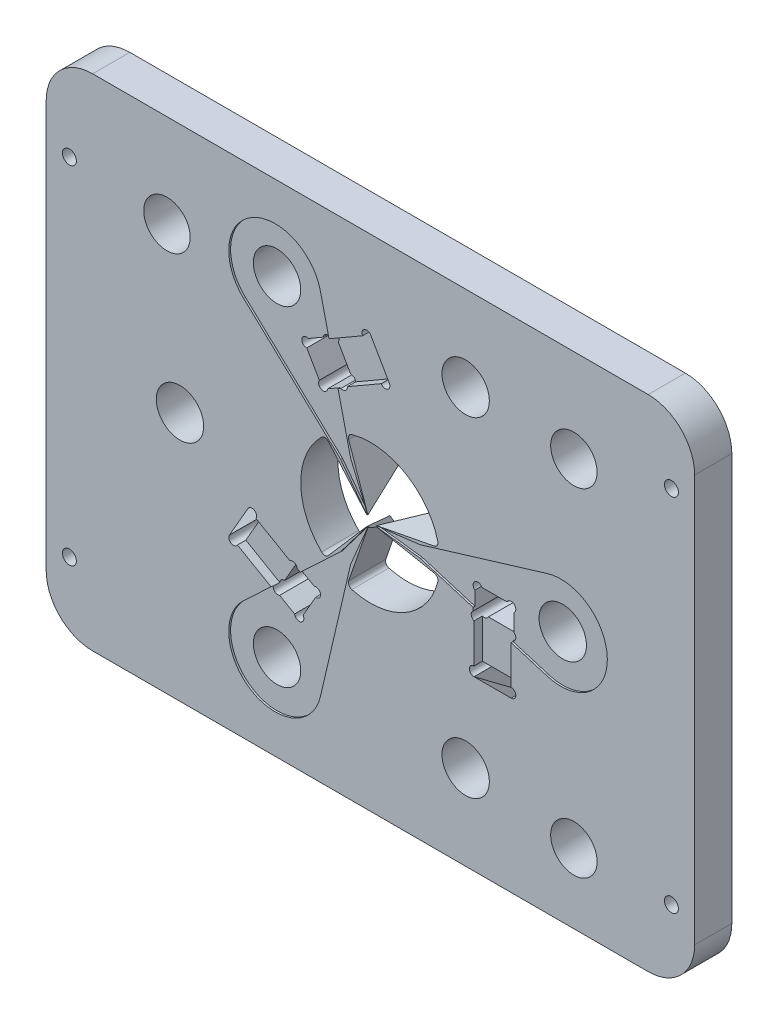
SolidWorks part; units mm, degrees
ref_plane "前基準面" through (0, 0, 0) normal (0, 0, 1) x (1, 0, 0)
ref_plane "上基準面" through (0, 0, 0) normal (0, 1, 0) x (1, 0, 0)
ref_plane "右基準面" through (0, 0, 0) normal (1, 0, 0) x (0, 0, -1)
sketch "草圖1" plane through (0, 0, 0) normal (0, 0, 1) x (1, 0, 0)
  line L1 (-38, 30) -> (38, 30)
  line L2 (-38, 30) -> (-38, -30)
  line L3 (-38, -30) -> (38, -30)
  line L4 (38, 30) -> (38, -30)
  line L5 (-38, 30) -> (38, -30) construction
  line L6 (-38, -30) -> (38, 30) construction
  point P0 (0, 0)
  point P28 (0, 0)
  dimension "D1" = 76
  dimension "D2" = 60
extrude "填料-伸長1" add sketch "草圖1" along normal blind 4
sketch "草圖2" plane through (0, 0, 4) normal (0, 0, 1) x (1, 0, 0)
  line L6 (0.3574, 0.005) -> (20.1903, 2.4807) construction
  line L7 (0.3574, -0.005) -> (20.1903, -2.4807) construction
  line L8 (0.3574, 0.005) -> (4.5094, 0.5233)
  line L9 (0.3574, -0.005) -> (4.5094, -0.5233)
  line L10 (6.1751, 0.8773) -> (19.0478, 4.7845)
  line L11 (6.1751, -0.8773) -> (19.0478, -4.7845)
  line L12 (-2.3278, -5.7864) -> (-5.3804, -18.8881)
  line L13 (-0.1744, -0.312) -> (-1.8015, -4.1669)
  line L14 (-0.183, -0.307) -> (-2.7079, -3.6436)
  line L15 (-3.8473, -4.9091) -> (-13.6674, -14.1037)
  line L16 (-3.8473, 4.9091) -> (-13.6674, 14.1037)
  line L17 (-0.183, 0.307) -> (-2.7079, 3.6436)
  line L18 (-0.1744, 0.312) -> (-1.8015, 4.1669)
  line L19 (-2.3278, 5.7864) -> (-5.3804, 18.8881)
  circle A7 centre (0, 0) radius 0.353 construction
  arc A8 (0.3574, 0.005) -> (0.3574, -0.005) centre (0.358, 0) ccw
  arc A9 (19.0478, -4.7845) -> (19.0478, 4.7845) centre (20.5, 0) ccw
  circle A10 centre (20.5, 0) radius 2.5 construction
  arc A11 (4.5094, -0.5233) -> (6.1751, -0.8773) centre (3.2707, -10.4463) cw
  arc A12 (4.5094, 0.5233) -> (6.1751, 0.8773) centre (3.2707, 10.4463) ccw
  arc A13 (-13.6674, -14.1037) -> (-5.3804, -18.8881) centre (-10.25, -17.7535) ccw
  arc A14 (-1.8015, -4.1669) -> (-2.3278, -5.7864) centre (7.4114, -8.0556) ccw
  arc A15 (-0.1744, -0.312) -> (-0.183, -0.307) centre (-0.179, -0.31) ccw
  arc A16 (-2.7079, -3.6436) -> (-3.8473, -4.9091) centre (-10.6821, 2.3906) cw
  arc A17 (-5.3804, 18.8881) -> (-13.6674, 14.1037) centre (-10.25, 17.7535) ccw
  arc A18 (-2.7079, 3.6436) -> (-3.8473, 4.9091) centre (-10.6821, -2.3906) ccw
  arc A19 (-0.183, 0.307) -> (-0.1744, 0.312) centre (-0.179, 0.31) ccw
  arc A20 (-1.8015, 4.1669) -> (-2.3278, 5.7864) centre (7.4114, 8.0556) cw
  point P17 (5.3574, -0.6291)
  point P20 (5.3574, 0.6291)
  point P46 (0, 0)
  dimension "D1" = 0.706
  dimension "D2" = 0.01
  dimension "D3" = 10
  dimension "D6" = 5
  dimension "D4" = 5
  dimension "D7" = 10
  dimension "D9" = 0.6201
  dimension "D5" = 20.5
  dimension "D8" = 3
extrude "除料-伸長1" cut sketch "草圖2" against normal blind 0.5
sketch "草圖3" plane through (0, 0, 3.5) normal (0, 0, 1) x (1, 0, 0)
  circle A0 centre (20.5, 0) radius 2.55
  circle A3 centre (-10.25, -17.7535) radius 2.55
  circle A4 centre (-10.25, 17.7535) radius 2.55
  point P9 (0, 0)
  dimension "D1" = 5.1
  dimension "D2" = 3
extrude "除料-伸長2" cut sketch "草圖3" against normal through all
sketch "草圖5" plane through (0, 0, 4) normal (0, 0, 1) x (1, 0, 0)
  circle A0 centre (-20.5, 0) radius 2.55
  circle A3 centre (10.25, 17.7535) radius 2.55
  circle A4 centre (10.25, -17.7535) radius 2.55
  point P9 (0, 0)
  dimension "D1" = 5.1
  dimension "D3" = 3
  dimension "D2" = 20.5
extrude "除料-伸長4" cut sketch "草圖5" against normal through all
sketch "草圖6" plane through (0, 0, 4) normal (0, 0, 1) x (1, 0, 0)
  line L0 (-29.9, 26.9) -> (29.9, 26.9)
  line L1 (-38, 30) -> (-38, -30) construction
  line L2 (38, -30) -> (38, 30) construction
  line L3 (-29.9, -26.9) -> (29.9, -26.9)
  line L4 (38, 30) -> (-38, 30) construction
  line L5 (-38, -30) -> (38, -30) construction
  line L6 (-34.9, 21.9) -> (-34.9, -21.9)
  line L7 (34.9, 21.9) -> (34.9, -21.9)
  arc A0 (34.9, 21.9) -> (29.9, 26.9) centre (29.9, 21.9) ccw
  arc A1 (29.9, -26.9) -> (34.9, -21.9) centre (29.9, -21.9) ccw
  arc A2 (-29.9, -26.9) -> (-34.9, -21.9) centre (-29.9, -21.9) cw
  arc A3 (-34.9, 21.9) -> (-29.9, 26.9) centre (-29.9, 21.9) cw
  line M32 (38, -30) -> (38, 30)
  line M33 (38, 30) -> (-38, 30)
  line M34 (-38, 30) -> (-38, -30)
  line M35 (-38, -30) -> (38, -30)
  dimension "D5" = 5
  dimension "D1" = 3.1
  dimension "D2" = 3.1
  dimension "D3" = 3.1
  dimension "D4" = 3.1
extrude "除料-伸長5" cut sketch "草圖6" against normal blind 10 contours L6 A3 L0 A0 L7 A1 L3 A2 M35 M32 M33 M34 region at (0, -29.0317, 4)
ref_plane "平面1" through (0, 0, 4) normal (0, 0, 1) x (1, 0, 0)
sketch "草圖7" plane through (0, 0, 4) normal (0, 0, 1) x (1, 0, 0)
  line L0 (0, 0) -> (34.9, 0) construction
  line L1 (34.9, 21.9) -> (34.9, -21.9) construction
  line L2 (11.05, -0.2286) -> (15.25, -0.2286)
  line L3 (15.25, -0.2286) -> (15.25, -3.3286)
  line L4 (15.25, -3.3286) -> (11.05, -3.3286)
  line L5 (11.05, -3.3286) -> (11.05, -0.2286)
  line L6 (13.15, -0.2286) -> (13.15, -3.3286) construction
  line L7 (11.05, -1.7786) -> (15.25, -1.7786) construction
  line L8 (13.15, -1.7786) -> (11.05, -0.2286) construction
  line L13 (0, 0) -> (-12.75, 22.0836) construction
  line L14 (-6.575, 11.3882) -> (11.1068, 21.5968) construction
  line L15 (-7.4271, 13.3212) -> (-5.3271, 9.6839)
  line L20 (-7.4271, 13.3212) -> (-4.7424, 14.8712)
  line L21 (-4.7424, 14.8712) -> (-2.6424, 11.2339)
  line L22 (-2.6424, 11.2339) -> (-5.3271, 9.6839)
  line L23 (13.15, -1.7786) -> (13.15, -13.7786) construction
  line L24 (11.15, -7.7786) -> (15.15, -7.7786)
  line L25 (15.15, -7.7786) -> (15.15, -8.7786)
  line L26 (15.15, -8.7786) -> (11.15, -8.7786)
  line L27 (11.15, -8.7786) -> (11.15, -7.7786)
  line L28 (11.15, -8.2786) -> (15.15, -8.2786) construction
  line L29 (-6.0847, 14.0962) -> (-3.9847, 10.4589) construction
  line L34 (-7.4271, 13.3212) -> (-2.6424, 11.2339) construction
  line L35 (-4.7424, 14.8712) -> (-5.3271, 9.6839) construction
  line L40 (-0.8386, 17.0096) -> (1.1614, 13.5455)
  line L41 (-0.8386, 17.0096) -> (0.0275, 17.5096)
  line L42 (0.0275, 17.5096) -> (2.0275, 14.0455)
  line L43 (2.0275, 14.0455) -> (1.1614, 13.5455)
  line L44 (-0.4055, 17.2596) -> (1.5945, 13.7955) construction
  line L45 (0, 0) -> (-12.75, -22.0836) construction
  line L46 (-6.575, -11.3882) -> (-21.3666, -2.8483) construction
  line L47 (-5.7229, -9.4553) -> (-7.8229, -13.0926)
  line L48 (-5.7229, -9.4553) -> (-8.4076, -7.9053)
  line L49 (-8.4076, -7.9053) -> (-10.5076, -11.5426)
  line L50 (-10.5076, -11.5426) -> (-7.8229, -13.0926)
  line L51 (-7.0653, -8.6803) -> (-9.1653, -12.3176) construction
  line L52 (-8.4076, -7.9053) -> (-7.8229, -13.0926) construction
  line L53 (-10.5076, -11.5426) -> (-5.7229, -9.4553) construction
  line L54 (-12.3114, -5.7669) -> (-14.3114, -9.231)
  line L55 (-12.3114, -5.7669) -> (-13.1775, -5.2669)
  line L56 (-13.1775, -5.2669) -> (-15.1775, -8.731)
  line L57 (-15.1775, -8.731) -> (-14.3114, -9.231)
  line L58 (-12.7445, -5.5169) -> (-14.7445, -8.981) construction
  line L59 (-4.7841, 14.5007) -> (-3.8841, 12.9418) construction
  line L60 (-10.1659, -11.3935) -> (-9.2659, -9.8347) construction
  circle A0 centre (11.35, -0.45) radius 0.5
  circle A1 centre (14.95, -0.45) radius 0.5
  circle A2 centre (14.95, -3.1071) radius 0.5
  circle A3 centre (11.35, -3.1071) radius 0.5
  circle A4 centre (13.15, -0.9886) radius 0.15 construction
  arc A11 (-5.3804, 18.8881) -> (-13.6674, 14.1037) centre (-10.25, 17.7535) ccw construction
  circle A17 centre (-7.0853, 13.1721) radius 0.5
  circle A18 centre (11.15, -8.2786) radius 0.5
  circle A19 centre (15.15, -8.2786) radius 0.5
  circle A24 centre (-4.7841, 14.5007) radius 0.5
  circle A25 centre (-2.9841, 11.383) radius 0.5
  circle A26 centre (-5.2853, 10.0544) radius 0.5
  circle A27 centre (-0.4055, 17.2596) radius 0.5
  circle A28 centre (1.5945, 13.7955) radius 0.5
  arc A29 (-13.6674, -14.1037) -> (-5.3804, -18.8881) centre (-10.25, -17.7535) ccw construction
  circle A30 centre (-6.0647, -9.6044) radius 0.5
  circle A31 centre (-7.8647, -12.7221) radius 0.5
  circle A32 centre (-10.1659, -11.3935) radius 0.5
  circle A33 centre (-8.3659, -8.2758) radius 0.5
  circle A34 centre (-14.7445, -8.981) radius 0.5
  circle A35 centre (-12.7445, -5.5169) radius 0.5
  point P36 (-6.3771, 11.5025)
  point P43 (0.1614, 15.2775)
  point P66 (-6.7729, -11.2739)
  point P72 (13.15, -7.7786)
  point P81 (-13.3114, -7.4989)
  dimension "D3" = 1
  dimension "D4" = 0.3
  dimension "D10" = 13.15
  dimension "D16" = 1
  dimension "D19" = 4
  dimension "D26" = 1
  dimension "D1" = 4.2
  dimension "D2" = 3.1
  dimension "D5" = 0.79
  dimension "D8" = 0.45
  dimension "D9" = 13.15
  dimension "D11" = 4.2
  dimension "D12" = 3.1
  dimension "D13" = 4
  dimension "D14" = 1
  dimension "D15" = 4.95
  dimension "D17" = 0.3
  dimension "D18" = 0.45
  dimension "D20" = 1
  dimension "D21" = 4.95
  dimension "D22" = 0.3
  dimension "D23" = 13.15
  dimension "D24" = 4.2
  dimension "D25" = 3.1
  dimension "D27" = 0.3
  dimension "D28" = 0.45
  dimension "D29" = 4
  dimension "D30" = 1
  dimension "D31" = 4.95
extrude "除料-伸長6" cut sketch "草圖7" against normal through all contours A17 | A28 L42 A27 L40 | L48 A33 L49 A32 L50 A31 L47 A30 | A35 L56 A34 L54 | A1 | A0 | L5 L2 L3 L4 | A3 | A2 | A17 | A19 | L26 L27 L24 L25 | A18 | A24 | A26 | A25 | A28 | A27 | A31 | A32 | A30 | A33 | A35 | A34 region at (-5.0347, 12.2775, 4) region at (0.5945, 15.5275, 4) region at (-8.1153, -10.4989, 4) region at (-13.7445, -7.2489, 4)
sketch "草圖8" plane through (0, 0, 0) normal (0, 0, 1) x (1, 0, 0)
  line L0 (-34.9, 21.9) -> (-24.9, 21.9) construction
  line L1 (-24.9, 21.9) -> (-24.9, -21.9) construction
  line L2 (-24.9, -21.9) -> (-34.9, -21.9) construction
  line L3 (-34.9, -21.9) -> (-34.9, 21.9) construction
  line L4 (-34.9, 0) -> (34.9, 0) construction
  line L5 (34.9, 21.9) -> (34.9, -21.9) construction
  line L6 (0, 26.9) -> (0, -26.9) construction
  line L7 (-29.9, 26.9) -> (29.9, 26.9) construction
  line L8 (-29.9, -26.9) -> (29.9, -26.9) construction
  circle A0 centre (-32.4, 17.9) radius 0.75
  circle A3 centre (32.4, 19.4) radius 0.75
  circle A4 centre (32.4, -19.4) radius 0.75
  circle A5 centre (-32.4, -19.4) radius 0.75
  dimension "D2" = 1.5
  dimension "D5" = 1.5
  dimension "D7" = 2.5
  dimension "D1" = 10
  dimension "D3" = 4
  dimension "D4" = 2.5
  dimension "D6" = 2.5
extrude "除料-伸長7" cut sketch "草圖8" along normal through all contours A3 | A5 | A4 | A0 region at (32.4, 19.4, 0) region at (-32.4, -19.4, 0)
sketch "草圖10" plane through (0, 0, 3.5) normal (0, 0, 1) x (1, 0, 0)
  line L48 (-3.8473, -4.9091) -> (-7.5662, -8.3911) construction
  line L49 (-7.5662, -8.3911) -> (-6.2611, -9.1446) construction
  line L50 (-6.0971, -10.1033) -> (-7.4488, -12.4446) construction
  line L51 (-8.3611, -12.7819) -> (-9.9695, -11.8533) construction
  line L52 (-10.6531, -11.2814) -> (-13.6674, -14.1037) construction
  line L53 (-5.3804, -18.8881) -> (-2.3278, -5.7864) construction
  line L54 (-1.8015, -4.1669) -> (-0.1744, -0.312) construction
  line L55 (-0.183, -0.307) -> (-2.7079, -3.6436) construction
  line L56 (11.05, -2.357) -> (11.05, -0.85) construction
  line L57 (11.7983, -0.2286) -> (14.5017, -0.2286) construction
  line L58 (15.25, -0.85) -> (15.25, -2.7071) construction
  line L59 (15.0966, -3.5852) -> (19.0478, -4.7845) construction
  line L60 (19.0478, 4.7845) -> (6.1751, 0.8773) construction
  line L61 (4.5094, 0.5233) -> (0.3574, 0.005) construction
  line L62 (0.3574, -0.005) -> (4.5094, -0.5233) construction
  line L63 (6.1751, -0.8773) -> (11.05, -2.357) construction
  line L64 (-3.4838, 10.7481) -> (-4.7889, 9.9946) construction
  line L65 (-5.7012, 10.3319) -> (-7.0529, 12.6731) construction
  line L66 (-6.8889, 13.6319) -> (-5.2805, 14.5605) construction
  line L67 (-4.4434, 14.8666) -> (-5.3804, 18.8881) construction
  line L68 (-13.6674, 14.1037) -> (-3.8473, 4.9091) construction
  line L69 (-2.7079, 3.6436) -> (-0.183, 0.307) construction
  line L70 (-0.1744, 0.312) -> (-1.8015, 4.1669) construction
  line L71 (-2.3278, 5.7864) -> (-3.4838, 10.7481) construction
  line L72 (-3.8473, -4.9091) -> (-7.5662, -8.3911)
  line L73 (-7.5662, -8.3911) -> (-6.2611, -9.1446)
  line L74 (-6.0971, -10.1033) -> (-7.4488, -12.4446)
  line L75 (-8.3611, -12.7819) -> (-9.9695, -11.8533)
  line L76 (-10.6531, -11.2814) -> (-13.6674, -14.1037)
  line L77 (-5.3804, -18.8881) -> (-2.3278, -5.7864)
  line L78 (-1.8015, -4.1669) -> (-0.1744, -0.312)
  line L79 (-0.183, -0.307) -> (-2.7079, -3.6436)
  line L80 (11.05, -2.357) -> (11.05, -0.85)
  line L81 (11.7983, -0.2286) -> (14.5017, -0.2286)
  line L82 (15.25, -0.85) -> (15.25, -2.7071)
  line L83 (15.0966, -3.5852) -> (19.0478, -4.7845)
  line L84 (19.0478, 4.7845) -> (6.1751, 0.8773)
  line L85 (4.5094, 0.5233) -> (0.3574, 0.005)
  line L86 (0.3574, -0.005) -> (4.5094, -0.5233)
  line L87 (6.1751, -0.8773) -> (11.05, -2.357)
  line L88 (-3.4838, 10.7481) -> (-4.7889, 9.9946)
  line L89 (-5.7012, 10.3319) -> (-7.0529, 12.6731)
  line L90 (-6.8889, 13.6319) -> (-5.2805, 14.5605)
  line L91 (-4.4434, 14.8666) -> (-5.3804, 18.8881)
  line L92 (-13.6674, 14.1037) -> (-3.8473, 4.9091)
  line L93 (-2.7079, 3.6436) -> (-0.183, 0.307)
  line L94 (-0.1744, 0.312) -> (-1.8015, 4.1669)
  line L95 (-2.3278, 5.7864) -> (-3.4838, 10.7481)
  circle A42 centre (-10.25, 17.7535) radius 2.55
  circle A43 centre (-10.25, -17.7535) radius 2.55
  circle A44 centre (20.5, 0) radius 2.55
  arc A45 (-6.0971, -10.1033) -> (-6.2611, -9.1446) centre (-6.0647, -9.6044) ccw construction
  arc A46 (-8.3611, -12.7819) -> (-7.4488, -12.4446) centre (-7.8647, -12.7221) ccw construction
  arc A47 (-10.6531, -11.2814) -> (-9.9695, -11.8533) centre (-10.1659, -11.3935) ccw construction
  arc A48 (-13.6674, -14.1037) -> (-5.3804, -18.8881) centre (-10.25, -17.7535) ccw construction
  arc A49 (-1.8015, -4.1669) -> (-2.3278, -5.7864) centre (7.4114, -8.0556) ccw construction
  arc A50 (-0.1744, -0.312) -> (-0.183, -0.307) centre (-0.179, -0.31) ccw construction
  arc A51 (-3.8473, -4.9091) -> (-2.7079, -3.6436) centre (-10.6821, 2.3906) ccw construction
  arc A52 (11.7983, -0.2286) -> (11.05, -0.85) centre (11.35, -0.45) ccw construction
  arc A53 (15.25, -0.85) -> (14.5017, -0.2286) centre (14.95, -0.45) ccw construction
  arc A54 (15.0966, -3.5852) -> (15.25, -2.7071) centre (14.95, -3.1071) ccw construction
  arc A55 (19.0478, -4.7845) -> (19.0478, 4.7845) centre (20.5, 0) ccw construction
  arc A56 (4.5094, 0.5233) -> (6.1751, 0.8773) centre (3.2707, 10.4463) ccw construction
  arc A57 (0.3574, 0.005) -> (0.3574, -0.005) centre (0.358, 0) ccw construction
  arc A58 (6.1751, -0.8773) -> (4.5094, -0.5233) centre (3.2707, -10.4463) ccw construction
  arc A59 (-5.7012, 10.3319) -> (-4.7889, 9.9946) centre (-5.2853, 10.0544) ccw construction
  arc A60 (-6.8889, 13.6319) -> (-7.0529, 12.6731) centre (-7.0853, 13.1721) ccw construction
  arc A61 (-4.4434, 14.8666) -> (-5.2805, 14.5605) centre (-4.7841, 14.5007) ccw construction
  arc A62 (-5.3804, 18.8881) -> (-13.6674, 14.1037) centre (-10.25, 17.7535) ccw construction
  arc A63 (-2.7079, 3.6436) -> (-3.8473, 4.9091) centre (-10.6821, -2.3906) ccw construction
  arc A64 (-0.183, 0.307) -> (-0.1744, 0.312) centre (-0.179, 0.31) ccw construction
  arc A65 (-2.3278, 5.7864) -> (-1.8015, 4.1669) centre (7.4114, 8.0556) ccw construction
  arc A66 (-6.0971, -10.1033) -> (-6.2611, -9.1446) centre (-6.0647, -9.6044) ccw
  arc A67 (-8.3611, -12.7819) -> (-7.4488, -12.4446) centre (-7.8647, -12.7221) ccw
  arc A68 (-10.6531, -11.2814) -> (-9.9695, -11.8533) centre (-10.1659, -11.3935) ccw
  arc A69 (-13.6674, -14.1037) -> (-5.3804, -18.8881) centre (-10.25, -17.7535) ccw
  arc A70 (-1.8015, -4.1669) -> (-2.3278, -5.7864) centre (7.4114, -8.0556) ccw
  arc A71 (-0.1744, -0.312) -> (-0.183, -0.307) centre (-0.179, -0.31) ccw
  arc A72 (-3.8473, -4.9091) -> (-2.7079, -3.6436) centre (-10.6821, 2.3906) ccw
  arc A73 (11.7983, -0.2286) -> (11.05, -0.85) centre (11.35, -0.45) ccw
  arc A74 (15.25, -0.85) -> (14.5017, -0.2286) centre (14.95, -0.45) ccw
  arc A75 (15.0966, -3.5852) -> (15.25, -2.7071) centre (14.95, -3.1071) ccw
  arc A76 (19.0478, -4.7845) -> (19.0478, 4.7845) centre (20.5, 0) ccw
  arc A77 (4.5094, 0.5233) -> (6.1751, 0.8773) centre (3.2707, 10.4463) ccw
  arc A78 (0.3574, 0.005) -> (0.3574, -0.005) centre (0.358, 0) ccw
  arc A79 (6.1751, -0.8773) -> (4.5094, -0.5233) centre (3.2707, -10.4463) ccw
  arc A80 (-5.7012, 10.3319) -> (-4.7889, 9.9946) centre (-5.2853, 10.0544) ccw
  arc A81 (-6.8889, 13.6319) -> (-7.0529, 12.6731) centre (-7.0853, 13.1721) ccw
  arc A82 (-4.4434, 14.8666) -> (-5.2805, 14.5605) centre (-4.7841, 14.5007) ccw
  arc A83 (-5.3804, 18.8881) -> (-13.6674, 14.1037) centre (-10.25, 17.7535) ccw
  arc A84 (-2.7079, 3.6436) -> (-3.8473, 4.9091) centre (-10.6821, -2.3906) ccw
  arc A85 (-0.183, 0.307) -> (-0.1744, 0.312) centre (-0.179, 0.31) ccw
  arc A86 (-2.3278, 5.7864) -> (-1.8015, 4.1669) centre (7.4114, 8.0556) ccw
  dimension "D1" = 5.1
  dimension "D2" = 5.1
  dimension "D3" = 5.1
extrude "填料-伸長2" add sketch "草圖10" along normal blind 0.5
sketch "草圖11" plane through (0, 0, 4) normal (0, 0, 1) x (1, 0, 0)
  line L0 (20.1778, 2.5296) -> (0.3574, 0.005) construction
  line L1 (0.3574, -0.005) -> (20.1778, -2.5296) construction
  line L2 (0.3574, 0.005) -> (5.3574, 0.6418) construction
  line L3 (0.3574, -0.005) -> (5.3574, -0.6418) construction
  line L4 (5.3574, 0.6418) -> (19.0519, 4.7857) construction
  line L5 (5.3574, -0.6418) -> (19.0519, -4.7857) construction
  line L6 (-0.183, -0.307) -> (-3.2345, -4.3187) construction
  line L7 (-3.2345, -4.3187) -> (-13.6705, -14.1066) construction
  line L8 (-2.1228, -4.9605) -> (-5.3814, -18.8923) construction
  line L9 (-0.1744, -0.312) -> (-2.1228, -4.9605) construction
  line L10 (-0.1744, 0.312) -> (-2.1228, 4.9605) construction
  line L11 (-2.1228, 4.9605) -> (-5.3814, 18.8923) construction
  line L12 (-3.2345, 4.3187) -> (-13.6705, 14.1066) construction
  line L13 (-0.183, 0.307) -> (-3.2345, 4.3187) construction
  line L14 (-0.1744, 0.312) -> (-2.1228, 4.9605) construction
  line L16 (-0.183, 0.307) -> (-3.2345, 4.3187) construction
  line L18 (-0.1744, -0.312) -> (-2.1228, -4.9605) construction
  line L20 (-0.183, -0.307) -> (-3.2345, -4.3187) construction
  line L22 (0.3574, -0.005) -> (5.3574, -0.6418) construction
  line L24 (0.3574, 0.005) -> (5.3574, 0.6418) construction
  line L26 (6.872, 1.2601) -> (0.3574, 0.005)
  line L27 (6.872, -1.2601) -> (0.3574, -0.005)
  line L32 (-2.3448, -6.5814) -> (-0.1744, -0.312)
  line L33 (-4.5273, -5.3213) -> (-0.183, -0.307)
  line L34 (-4.5273, 5.3213) -> (-0.183, 0.307)
  line L35 (-2.3448, 6.5814) -> (-0.1744, 0.312)
  circle A0 centre (0, 0) radius 0.353 construction
  arc A1 (0.3574, 0.005) -> (0.3574, -0.005) centre (0.358, 0) ccw construction
  circle A4 centre (20.5, 0) radius 2.55 construction
  circle A5 centre (20.5, 0) radius 2.55 construction
  arc A6 (19.0519, -4.7857) -> (19.0519, 4.7857) centre (20.5, 0) ccw construction
  arc A7 (-0.1744, -0.312) -> (-0.183, -0.307) centre (-0.179, -0.31) ccw construction
  arc A8 (-13.6705, -14.1066) -> (-5.3814, -18.8923) centre (-10.25, -17.7535) ccw construction
  arc A9 (-0.183, 0.307) -> (-0.1744, 0.312) centre (-0.179, 0.31) ccw construction
  arc A10 (-5.3814, 18.8923) -> (-13.6705, 14.1066) centre (-10.25, 17.7535) ccw construction
  arc A12 (-0.183, 0.307) -> (-0.1744, 0.312) centre (-0.179, 0.31) ccw
  arc A13 (-0.1744, -0.312) -> (-0.183, -0.307) centre (-0.179, -0.31) ccw
  arc A15 (0.3574, 0.005) -> (0.3574, -0.005) centre (0.358, 0) ccw
  arc A22 (-5.2555, 5.3506) -> (-5.2555, -5.3506) centre (0, 0) ccw
  arc A23 (-2.006, -7.2267) -> (7.2616, -1.8761) centre (0, 0) ccw
  arc A24 (7.2616, 1.8761) -> (-2.006, 7.2267) centre (0, 0) ccw
  arc A25 (6.872, 1.2601) -> (7.2616, 1.8761) centre (6.7775, 1.751) ccw
  arc A26 (6.872, -1.2601) -> (7.2616, -1.8761) centre (6.7775, -1.751) cw
  arc A27 (-2.3448, -6.5814) -> (-2.006, -7.2267) centre (-1.8723, -6.745) ccw
  arc A28 (-4.5273, -5.3213) -> (-5.2555, -5.3506) centre (-4.9052, -4.9939) cw
  arc A29 (-4.5273, 5.3213) -> (-5.2555, 5.3506) centre (-4.9052, 4.9939) ccw
  arc A30 (-2.3448, 6.5814) -> (-2.006, 7.2267) centre (-1.8723, 6.745) cw
  point P35 (0, 0)
  point P45 (7.3762, 1.3572)
  point P48 (0, 0)
  point P52 (7.3762, -1.3572)
  dimension "D1" = 0.706
  dimension "D2" = 0.01
  dimension "D3" = 5
  dimension "D4" = 10
  dimension "D6" = 15
  dimension "D7" = 0.1
  dimension "D10" = 0.5
  dimension "D11" = 0.5
  dimension "D12" = 0.5
  dimension "D13" = 0.5
  dimension "D14" = 0.5
  dimension "D15" = 0.5
  dimension "D8" = 0.1
  dimension "D9" = 3
  dimension "D5" = 3
extrude "除料-伸長9" cut sketch "草圖11" against normal through all
sketch "草圖12" plane through (0, 0, 0) normal (0, 1, 0) x (1, 0, 0)
  line L0 (0, 0) -> (0, -5.1664) construction
  line L2 (-29.9, 0) -> (29.9, 0) construction
  line L6 (0.353, -4.18) -> (0.353, 0)
  line L7 (0.353, 0) -> (2.7663, 0)
  line L8 (2.7663, 0) -> (0.353, -4.18)
  line L9 (-29.59, -4) -> (29.59, -4) construction
  dimension "D1" = 0.353
  dimension "D2" = 0.18
  dimension "D3" = 30
revolve "除料-旋轉1" cut sketch "草圖12" angle 360 about L0
sketch "草圖13" plane through (0, 0, 0) normal (0, 0, -1) x (-1, 0, 0)
  line L0 (29.9, 26.9) -> (-29.9, 26.9) construction
  line L1 (-34.9, 21.9) -> (-34.9, -21.9) construction
  line L2 (0, 26.9) -> (0, -26.9) construction
  line L3 (29.9, -26.9) -> (-29.9, -26.9) construction
  circle A0 centre (-21.9, 16.9) radius 2.5
  circle A1 centre (21.9, 16.9) radius 2.5
  circle A2 centre (-21.9, -19.4) radius 2.5
  dimension "D1" = 5
  dimension "D4" = 5
  dimension "D2" = 10
  dimension "D3" = 13
  dimension "D5" = 7.5
extrude "除料-伸長10" cut sketch "草圖13" against normal through all
sketch "草圖14" plane through (0, 0, 4) normal (0, 0, 1) x (1, 0, 0)
  line L0 (13.15, -0.2286) -> (13.15, -8.7786) construction
  line L1 (11.7983, -0.2286) -> (14.5017, -0.2286) construction
  line L2 (15.15, -8.7786) -> (11.15, -8.7786) construction
  line L3 (14.2511, -3.3286) -> (11.7983, -3.3286) construction
  line L4 (11.15, -3.3286) -> (15.15, -3.3286)
  line L5 (11.15, -3.3286) -> (11.15, -7.7786)
  line L6 (11.15, -7.7786) -> (15.15, -7.7786)
  line L7 (15.15, -3.3286) -> (15.15, -7.7786)
  line L8 (11.15, -3.3286) -> (15.15, -7.7786) construction
  line L9 (11.15, -7.7786) -> (15.15, -3.3286) construction
  line L10 (-6.3771, 11.5025) -> (1.0275, 15.7775) construction
  line L11 (-5.7012, 10.3319) -> (-7.0529, 12.6731) construction
  line L12 (0.0275, 17.5096) -> (2.0275, 14.0455) construction
  line L14 (-4.6924, 14.7846) -> (-2.6924, 11.3205)
  line L15 (-4.6924, 14.7846) -> (-0.8386, 17.0096)
  line L16 (-0.8386, 17.0096) -> (1.1614, 13.5455)
  line L17 (-2.6924, 11.3205) -> (1.1614, 13.5455)
  line L18 (-4.6924, 14.7846) -> (1.1614, 13.5455) construction
  line L19 (-0.8386, 17.0096) -> (-2.6924, 11.3205) construction
  line L21 (-0.8386, 17.0096) -> (1.1614, 13.5455) construction
  line L22 (-4.2429, 14.0061) -> (-3.0165, 11.8819) construction
  line L23 (-6.7729, -11.2739) -> (-13.3114, -7.4989) construction
  line L24 (-6.0971, -10.1033) -> (-7.4488, -12.4446) construction
  line L25 (-12.3114, -5.7669) -> (-14.3114, -9.231) construction
  line L26 (-8.7818, -8.5533) -> (-10.0082, -10.6776) construction
  line L27 (-14.3114, -9.231) -> (-12.3114, -5.7669)
  line L28 (-14.3114, -9.231) -> (-10.4576, -11.456)
  line L29 (-10.4576, -11.456) -> (-8.4576, -7.9919)
  line L30 (-12.3114, -5.7669) -> (-8.4576, -7.9919)
  line L31 (-14.3114, -9.231) -> (-8.4576, -7.9919) construction
  line L32 (-10.4576, -11.456) -> (-12.3114, -5.7669) construction
  point P6 (13.15, -5.5536)
  point P20 (-1.7655, 14.165)
  point P29 (-11.3845, -8.6114)
extrude "除料-伸長11" cut sketch "草圖14" against normal blind 0.9
sketch "草圖15" plane through (0, 0, 0) normal (0, 1, 0) x (1, 0, 0)
  line L0 (0, 0) -> (0, -4.2669) construction
  line L1 (0.353, 0) -> (0.353, -4.18)
  line L6 (-29.59, -4) -> (29.59, -4) construction
  line L7 (0.353, -4.18) -> (0.553, -4.18)
  line L8 (0.553, -4.18) -> (2.9663, 0)
  line L9 (0.353, 0) -> (2.9663, 0)
  line L10 (-29.9, 0) -> (29.9, 0) construction
  dimension "D1" = 0.353
  dimension "D2" = 0.18
  dimension "D3" = 30
  dimension "D4" = 0.2
revolve "除料-旋轉2" cut sketch "草圖15" angle 360 about L0
sketch "草圖16" plane through (0, 0, 4) normal (0, 0, 1) x (1, 0, 0)
  line L0 (0.3574, 0.005) -> (20.1903, 2.4807) construction
  line L1 (20.1903, -2.4807) -> (0.3574, -0.005) construction
  line L2 (0.3574, 0.005) -> (5.358, 0.6292)
  line L3 (0.3574, -0.005) -> (5.358, -0.6292)
  line L4 (5.358, 0.6292) -> (19.0478, 4.7845)
  line L5 (5.358, -0.6292) -> (19.0478, -4.7845)
  line L6 (-0.183, -0.307) -> (-3.2239, -4.3256)
  line L7 (-3.2239, -4.3256) -> (-13.6673, -14.1036)
  line L8 (-2.1341, -4.9548) -> (-5.3804, -18.8881)
  line L9 (-0.1744, -0.312) -> (-2.1341, -4.9548)
  line L10 (-0.1744, -0.312) -> (-7.9468, -18.7257) construction
  line L11 (-12.2436, -16.245) -> (-0.183, -0.307) construction
  line L12 (-0.1744, 0.312) -> (-2.1341, 4.9548)
  line L13 (-2.1341, 4.9548) -> (-5.3804, 18.8881)
  line L14 (-3.2239, 4.3256) -> (-13.6673, 14.1036)
  line L15 (-0.183, 0.307) -> (-3.2239, 4.3256)
  line L16 (-0.183, 0.307) -> (-12.2436, 16.245) construction
  line L17 (-7.9468, 18.7257) -> (-0.1744, 0.312) construction
  circle A0 centre (0, 0) radius 0.353 construction
  arc A1 (0.3574, 0.005) -> (0.3574, -0.005) centre (0.358, 0) ccw
  circle A2 centre (20.5, 0) radius 2.5 construction
  arc A4 (19.0478, -4.7845) -> (19.0478, 4.7845) centre (20.5, 0) ccw
  arc A5 (-0.1744, -0.312) -> (-0.183, -0.307) centre (-0.179, -0.31) ccw
  arc A6 (-13.6673, -14.1036) -> (-5.3804, -18.8881) centre (-10.25, -17.7535) ccw
  circle A7 centre (-10.25, -17.7535) radius 2.5 construction
  arc A8 (-0.183, 0.307) -> (-0.1744, 0.312) centre (-0.179, 0.31) ccw
  arc A9 (-5.3804, 18.8881) -> (-13.6673, 14.1036) centre (-10.25, 17.7535) ccw
  circle A10 centre (-10.25, 17.7535) radius 2.5 construction
  point P39 (0, 0)
  dimension "D1" = 0.706
  dimension "D2" = 0.01
  dimension "D3" = 5
  dimension "D4" = 10
  dimension "D5" = 5
  dimension "D6" = 3
extrude "除料-伸長12" cut sketch "草圖16" against normal blind 0.2
ref_plane "平面2" through (11.15, 0, 0) normal (1, 0, 0) x (0, 0, -1)
sketch "草圖17" plane through (11.15, 0, 0) normal (1, 0, 0) x (0, 0, -1)
  line L7 (0, -11.7786) -> (0, -8.7786)
  line L8 (0, -10.1033) -> (0, -12.4446) construction
  line L9 (0, -8.7786) -> (0, -7.7786) construction
  line L10 (0, -5.7669) -> (0, -9.231) construction
  line L11 (0, -8.7786) -> (-4, -8.7786)
  line L12 (-4, 29.59) -> (-4, -29.59) construction
  line L14 (-4, -8.7786) -> (0, -11.7786)
  line L22 (-4, -8.7786) -> (0, -8.7786)
  line L23 (0, -8.7786) -> (0, -7.7786)
  line L24 (0, -7.7786) -> (-3.1, -7.7786)
  line L25 (-3.1, -7.7786) -> (-4, -7.7786)
  line L26 (-4, -7.7786) -> (-4, -8.7786)
  line L27 (-4, -8.7786) -> (0, -8.7786) construction
  line L28 (0, -8.7786) -> (0, -7.7786) construction
  line L29 (0, -7.7786) -> (-3.1, -7.7786) construction
  line L30 (-3.1, -7.7786) -> (-4, -7.7786) construction
  line L31 (-4, -7.7786) -> (-4, -8.7786) construction
  dimension "D1" = 3
  dimension "D2" = 0
extrude "除料-伸長15" cut sketch "草圖17" along normal blind 4
ref_plane "平面3" through (-5.575, 9.6562, 0) normal (-0.5, 0.866, 0) x (0.866, 0.5, 0)
sketch "草圖18" plane through (-5.575, 9.6562, 0) normal (-0.5, 0.866, 0) x (0.866, 0.5, 0)
  line L7 (8.7786, -4) -> (8.7786, 0)
  line L8 (8.7786, 0) -> (11.7786, 0)
  line L9 (10.1033, 0) -> (12.4446, 0) construction
  line L10 (11.7786, 0) -> (8.7786, -4)
  line L12 (7.7786, 0) -> (7.7786, -3.1)
  line L13 (7.7786, -3.1) -> (7.7786, -4)
  line L14 (7.7786, -4) -> (8.7786, -4)
  line L15 (8.7786, -4) -> (8.7786, 0)
  line L16 (8.7786, 0) -> (7.7786, 0)
  line L17 (7.7786, 0) -> (7.7786, -3.1) construction
  line L18 (7.7786, -3.1) -> (7.7786, -4) construction
  line L19 (7.7786, -4) -> (8.7786, -4) construction
  line L20 (8.7786, -4) -> (8.7786, 0) construction
  line L21 (8.7786, 0) -> (7.7786, 0) construction
  dimension "D1" = 3
  dimension "D2" = 0
extrude "除料-伸長16" cut sketch "草圖18" along normal blind 4
ref_plane "平面4" through (-5.575, -9.6562, 0) normal (-0.5, -0.866, 0) x (-0.866, 0.5, 0)
sketch "草圖19" plane through (-5.575, -9.6562, 0) normal (-0.5, -0.866, 0) x (-0.866, 0.5, 0)
  line L4 (8.7786, -4) -> (8.7786, 0)
  line L5 (7.7786, 0) -> (7.7786, -3.1)
  line L6 (7.7786, -3.1) -> (7.7786, -4)
  line L7 (7.7786, -4) -> (8.7786, -4)
  line L8 (8.7786, -4) -> (8.7786, 0)
  line L9 (8.7786, 0) -> (7.7786, 0)
  line L10 (7.7786, 0) -> (7.7786, -3.1) construction
  line L11 (7.7786, -3.1) -> (7.7786, -4) construction
  line L12 (7.7786, -4) -> (8.7786, -4) construction
  line L13 (8.7786, -4) -> (8.7786, 0) construction
  line L14 (8.7786, 0) -> (7.7786, 0) construction
  line L15 (8.7786, 0) -> (11.7786, 0)
  line L16 (12.4446, 0) -> (10.1033, 0) construction
  line L17 (11.7786, 0) -> (8.7786, -4)
  dimension "D2" = 3
  dimension "D1" = 0
extrude "除料-伸長17" cut sketch "草圖19" along normal blind 4
